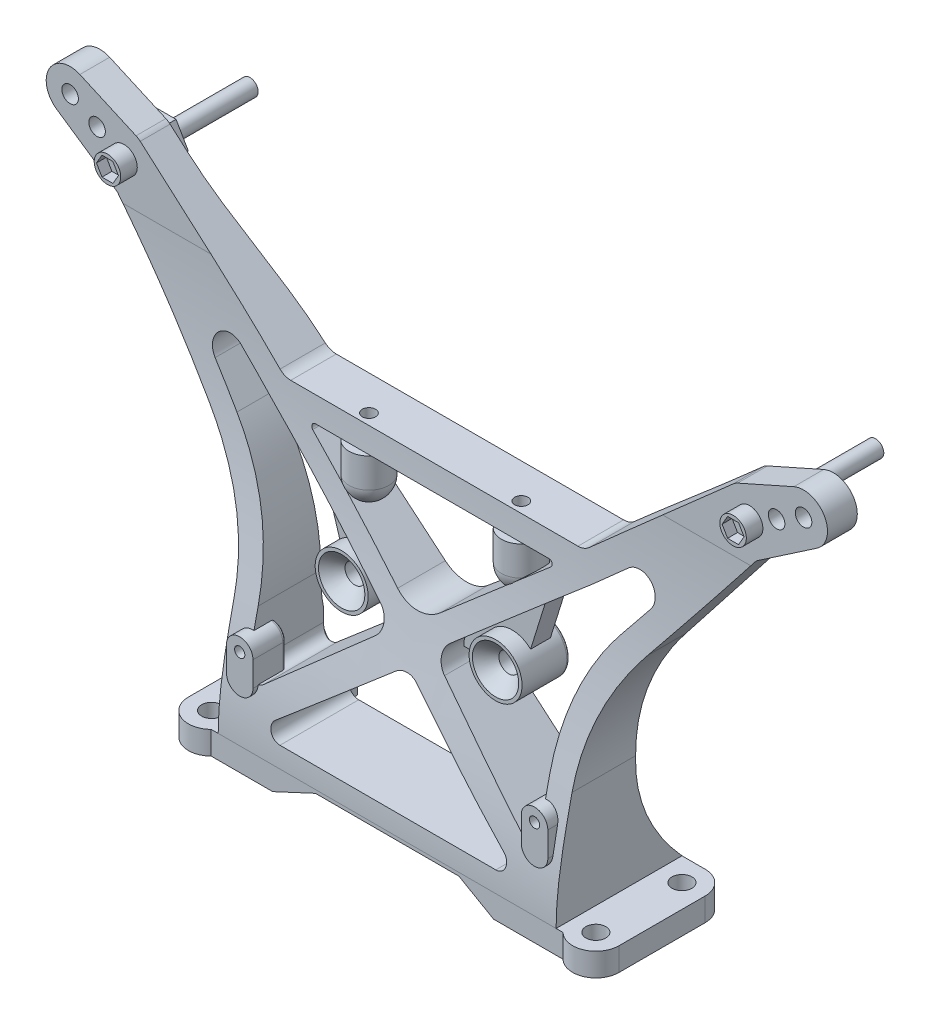
SolidWorks part; units mm, degrees
ref_plane "Front Plane" through (0, 0, 0) normal (0, 0, 1) x (1, 0, 0)
ref_plane "Top Plane" through (0, 0, 0) normal (0, 1, 0) x (1, 0, 0)
ref_plane "Right Plane" through (0, 0, 0) normal (1, 0, 0) x (0, 0, -1)
sketch "Sketch3" plane through (0, 0, 0) normal (0, 0, 1) x (1, 0, 0)
  line L0 (-16.289, -29.1062) -> (16.289, -29.1062)
  line L1 (17.2472, -26.4522) -> (1.597, -13.4575)
  line L2 (-1.597, -13.4575) -> (-17.2472, -26.4522)
  line L3 (32.5, -35.6062) -> (-32.5, -35.6062)
  line L4 (0, -35.6062) -> (0, 0) construction
  line L5 (-17.276, -35.6062) -> (-10.8295, -32.6062)
  line L6 (-10.8295, -32.6062) -> (10.8295, -32.6062)
  line L7 (10.8295, -32.6062) -> (16.0567, -35.6062)
  line L8 (0, -32.6062) -> (0, 0) construction
  line L9 (32.5, -35.6062) -> (32.5, -32.1062)
  line L10 (32.5, -32.1062) -> (25.5, -32.1062)
  line L11 (-32.5, -35.6062) -> (-32.5, -32.1062)
  line L12 (-32.5, -32.1062) -> (-25.5, -32.1062)
  line L13 (-25.5, -32.1062) -> (-25.5, -15.5226)
  line L14 (25.5, -32.1062) -> (-25.5, -32.1062) construction
  line L15 (0, -32.1062) -> (0, 0) construction
  line L16 (25.5, -32.1062) -> (25.5, -15.5226)
  line L17 (48.2113, 23.5519) -> (33.0635, 4.2389)
  line L18 (48.2113, 23.5519) -> (57.3809, 29.792)
  line L19 (53.8787, 36.0818) -> (45.3992, 32.3095)
  line L20 (47.2129, 28.2727) -> (55.3477, 32.7798) construction
  line L21 (44.7626, 31.9011) -> (23.3308, 13.018)
  line L22 (21.6781, 12.3938) -> (-21.6781, 12.3938)
  line L23 (-17.6357, 8.8938) -> (17.6357, 8.8938)
  line L24 (24.247, 8.8938) -> (29.2451, 13.2975)
  line L25 (32.8714, 9.8727) -> (29.0184, 4.9603)
  line L26 (22, -14.978) -> (22, -22.0285)
  line L27 (55.3477, 36.3938) -> (64.3873, 36.3938) construction
  line L28 (0, -29.1062) -> (0, 0) construction
  line L29 (24.247, 8.8938) -> (5.2406, -7.0999)
  line L30 (5.2234, -10.9109) -> (19.5239, -23.1674)
  line L31 (0, 8.8938) -> (0, 0) construction
  line L32 (0, 12.3938) -> (0, 0) construction
  line L33 (-55.3477, 36.3938) -> (-64.3873, 36.3938) construction
  line L34 (-47.2129, 28.2727) -> (-55.3477, 32.7798) construction
  line L35 (-5.2234, -10.9109) -> (-19.5239, -23.1674)
  line L36 (-24.247, 8.8938) -> (-5.2406, -7.0999)
  line L37 (-22, -14.978) -> (-22, -22.0285)
  line L38 (-32.8714, 9.8727) -> (-29.0184, 4.9603)
  line L39 (-24.247, 8.8938) -> (-29.2451, 13.2975)
  line L40 (-44.7626, 31.9011) -> (-23.3308, 13.018)
  line L41 (-53.8787, 36.0818) -> (-45.3992, 32.3095)
  line L42 (-48.2113, 23.5519) -> (-57.3809, 29.792)
  line L43 (-48.2113, 23.5519) -> (-33.0635, 4.2389)
  line L44 (-17.9576, 8.0112) -> (-3.2193, -4.3909)
  line L45 (3.2193, -4.3909) -> (17.9576, 8.0112)
  line L46 (0, 8.8938) -> (0, 0) construction
  arc A0 (57.3809, 29.792) -> (53.8787, 36.0818) centre (55.3477, 32.7798) ccw
  circle A1 centre (55.3477, 32.7798) radius 1.25
  circle A2 centre (51.2803, 30.5262) radius 1.25
  circle A3 centre (47.2129, 28.2727) radius 1.25
  arc A4 (29.2451, 13.2975) -> (32.8714, 9.8727) centre (30.9008, 11.4184) cw
  arc A5 (5.2406, -7.0999) -> (5.2234, -10.9109) centre (6.8503, -9.0127) ccw
  arc A6 (1.597, -13.4575) -> (-1.597, -13.4575) centre (0, -15.3809) ccw
  arc A7 (-17.2472, -26.4522) -> (-16.289, -29.1062) centre (-16.289, -27.6062) ccw
  arc A8 (22, -22.0285) -> (19.5239, -23.1674) centre (20.5, -22.0285) cw
  arc A9 (16.289, -29.1062) -> (17.2472, -26.4522) centre (16.289, -27.6062) ccw
  arc A10 (-5.2406, -7.0999) -> (-5.2234, -10.9109) centre (-6.8503, -9.0127) cw
  arc A11 (-22, -22.0285) -> (-19.5239, -23.1674) centre (-20.5, -22.0285) ccw
  arc A12 (-29.2451, 13.2975) -> (-32.8714, 9.8727) centre (-30.9008, 11.4184) ccw
  circle A13 centre (-47.2129, 28.2727) radius 1.25
  circle A14 centre (-51.2803, 30.5262) radius 1.25
  circle A15 centre (-55.3477, 32.7798) radius 1.25
  arc A16 (-57.3809, 29.792) -> (-53.8787, 36.0818) centre (-55.3477, 32.7798) cw
  arc A17 (-3.2193, -4.3909) -> (3.2193, -4.3909) centre (0, -0.5652) ccw
  arc A18 (17.6357, 8.8938) -> (17.9576, 8.0112) centre (17.6357, 8.3938) cw
  arc A19 (-17.9576, 8.0112) -> (-17.6357, 8.8938) centre (-17.6357, 8.3938) cw
  arc A20 (45.3992, 32.3095) -> (44.7626, 31.9011) centre (46.4154, 30.0253) ccw
  arc A21 (-44.7626, 31.9011) -> (-45.3992, 32.3095) centre (-46.4154, 30.0253) ccw
  arc A22 (23.3308, 13.018) -> (21.6781, 12.3938) centre (21.6781, 14.8938) cw
  arc A23 (-21.6781, 12.3938) -> (-23.3308, 13.018) centre (-21.6781, 14.8938) cw
  spline S0 degree 3 poles (25.5, -15.5226) (25.5, -7.9528) (28.6451, -1.3945) (33.0635, 4.2389) knots 0 0 0 0 1 1 1 1
  spline S1 degree 3 poles (22, -14.978) (22, -7.3515) (24.5868, -0.6899) (29.0184, 4.9603) knots 0 0 0 0 1 1 1 1
  spline S2 degree 3 poles (-22, -14.978) (-22, -7.3515) (-24.5868, -0.6899) (-29.0184, 4.9603) knots 0 0 0 0 1 1 1 1
  spline S3 degree 3 poles (-25.5, -15.5226) (-25.5, -7.9528) (-28.6451, -1.3945) (-33.0635, 4.2389) knots 0 0 0 0 1 1 1 1
  point P90 (0, -7.0999)
  point P97 (45.0497, 32.154)
  point P100 (-45.0497, 32.154)
  point P103 (22.6223, 12.3938)
  point P106 (-22.6223, 12.3938)
  dimension "D7" = 2.5
  dimension "D8" = 2.5
  dimension "D9" = 2.5
  dimension "D15" = 2.5
  dimension "D16" = 1.5
  dimension "D18" = 5
  dimension "D19" = 0.5
  dimension "D20" = 2.5
  dimension "D2" = 65
  dimension "D3" = 3
  dimension "D4" = 3.5
  dimension "D5" = 3.5
  dimension "D6" = 32.6062
  dimension "D10" = 72
  dimension "D11" = 48
  dimension "D12" = 3.5
  dimension "D13" = 25.5
  dimension "D14" = 3.5
  dimension "D17" = 45.2446
extrude "Boss-Extrude2" add sketch "Sketch3" along normal blind 8.5 and the other way blind 11.5 contours S3 L13 L12 L11 L3 L5 L6 L7 L9 L10 L16 S0 L17 L18 A0 L19 A20 L21 A22 L22 A23 L40 A21 L41 A16 L42 L43 S1 L26 A8 L30 A5 L29 L24 A4 L25 A14 A1 A2 A3 A9 L0 A7 L2 region at (24.2784, -34.2246, 0)
sketch "Sketch4" plane through (0, 0, 0) normal (1, 0, 0) x (0, 0, -1)
  line L0 (-8.5, -32.1062) -> (-7.5, -32.1062)
  line L1 (0, 36.3938) -> (0, 22.4957)
  line L2 (11.5, 36.3938) -> (-8.5, 36.3938) construction
  line L3 (0, 36.3938) -> (-8.5, 36.3938)
  line L4 (-8.5, 36.3938) -> (-8.5, 29.792) construction
  line L5 (-8.5, 36.3938) -> (-8.5, -32.1062)
  line L6 (4.5, 36.3938) -> (4.5, -16.1942)
  line L7 (4.5, 36.3938) -> (11.5, 36.3938)
  line L8 (11.5, 29.792) -> (11.5, 36.3938) construction
  line L9 (11.5, 36.3938) -> (11.5, -32.1062)
  line L10 (11.5, -32.1062) -> (-8.5, -32.1062) construction
  line L11 (-7.5, -32.1062) -> (-7.5, -34.5604) construction
  spline S0 degree 3 poles (-7.5, -32.1062) (-7.5, -18.2378) (0, -3.8629) (0, 22.4957) knots 0 0 0 0 1 1 1 1
  spline S1 degree 2 poles (4.5, -16.1942) (4.5, -24.3843) (11.5, -32.1062) knots 0 0 0 1 1 1
  dimension "D1" = 4.5
  dimension "D2" = 1
extrude "Cut-Extrude1" cut sketch "Sketch4" against normal through all and the other way through all contours L5 L1 L3 | L6 S1 region at (0, 10.6256, 4.9394) region at (0, 4.6469, -8.1165)
sketch "Sketch5" plane through (0, -35.6062, 0) normal (0, -1, 0) x (1, 0, 0)
  line L0 (-30.5, 5) -> (-30.5, 1.3765) construction
  line L1 (-29, 6.5) -> (-22.1667, 6.5) construction
  line L2 (-17.276, 8.5) -> (-32.5, 8.5) construction
  line L3 (-32.5, -11.5) -> (-32.5, 8.5) construction
  line L4 (-29, 3.5) -> (-29, -6.5) construction
  line L5 (-27.5, -8) -> (27.5, -8) construction
  line L6 (29, -6.5) -> (29, 3.5) construction
  line L7 (27.5, 5) -> (-27.5, 5) construction
  line L8 (-29, -9.5) -> (-25.3589, -9.5) construction
  line L9 (-17.276, -11.5) -> (-32.5, -11.5) construction
  line L10 (30.5, 5) -> (30.5, 0.9382) construction
  line L11 (32.5, -11.5) -> (32.5, 8.5) construction
  line L12 (32.5, -11.5) -> (16.0567, -11.5) construction
  line L13 (32.5, 8.5) -> (16.0567, 8.5) construction
  line L14 (26.5505, 7.5) -> (-26.5505, 7.5)
  line L15 (-29, -11.5) -> (-23.5, -11.5)
  line L16 (-23.5, -11.5) -> (-23.5, -7.5)
  line L17 (-20.5, -4.5) -> (-9.3284, -4.5)
  line L18 (-7.9142, -3.9142) -> (-6.0858, -2.0858)
  line L19 (-4.6716, -1.5) -> (4.6716, -1.5)
  line L20 (-33.0635, -4.5) -> (-48.2113, -4.5) construction
  line L21 (0, -1.5) -> (0, 0) construction
  line L22 (23.5, -11.5) -> (23.5, -7.5)
  line L23 (20.5, -4.5) -> (9.3284, -4.5)
  line L24 (7.9142, -3.9142) -> (6.0858, -2.0858)
  line L25 (-23.5, -11.5) -> (23.5, -11.5)
  line L26 (-29, -11.5) -> (-32.5, -11.5)
  line L27 (-32.5, -11.5) -> (-32.5, -8)
  line L28 (-32.5, 5) -> (-32.5, 8.5)
  line L29 (-32.5, 8.5) -> (-29, 8.5)
  line L30 (-29, 8.5) -> (29, 8.5)
  line L31 (29, 8.5) -> (32.5, 8.5)
  line L32 (32.5, 8.5) -> (32.5, 5)
  line L33 (32.5, -8) -> (32.5, -11.5)
  line L34 (32.5, -11.5) -> (29, -11.5)
  line L35 (9.3284, -4.5) -> (-9.3284, -4.5)
  circle A0 centre (-29, -8) radius 1.5
  circle A1 centre (-29, 5) radius 1.5
  circle A2 centre (29, 5) radius 1.5
  circle A3 centre (29, -8) radius 1.5
  arc A4 (-32.5, 5) -> (-29, 8.5) centre (-29, 5) cw
  arc A5 (-32.5, -8) -> (-29, -11.5) centre (-29, -8) ccw
  arc A6 (32.5, -8) -> (29, -11.5) centre (29, -8) cw
  arc A7 (32.5, 5) -> (29, 8.5) centre (29, 5) ccw
  arc A8 (-29, 8.5) -> (-26.5505, 7.5) centre (-29, 5) cw
  arc A9 (29, 8.5) -> (26.5505, 7.5) centre (29, 5) ccw
  arc A10 (-20.5, -4.5) -> (-23.5, -7.5) centre (-20.5, -7.5) ccw
  arc A11 (-4.6716, -1.5) -> (-6.0858, -2.0858) centre (-4.6716, -3.5) ccw
  arc A12 (-7.9142, -3.9142) -> (-9.3284, -4.5) centre (-9.3284, -2.5) cw
  arc A13 (20.5, -4.5) -> (23.5, -7.5) centre (20.5, -7.5) cw
  arc A14 (7.9142, -3.9142) -> (9.3284, -4.5) centre (9.3284, -2.5) ccw
  arc A15 (4.6716, -1.5) -> (6.0858, -2.0858) centre (4.6716, -3.5) cw
  point P55 (-23.5, -4.5)
  point P60 (-5.5, -1.5)
  point P63 (-8.5, -4.5)
  point P71 (8.5, -4.5)
  line M17 (32.5, -11.5) -> (32.5, 8.5)
  line M18 (32.5, 8.5) -> (16.0567, 8.5)
  line M19 (16.0567, 8.5) -> (16.0567, -11.5)
  line M20 (16.0567, -11.5) -> (32.5, -11.5)
  dimension "D3" = 3
  dimension "D4" = 3
  dimension "D5" = 3
  dimension "D6" = 3
  dimension "D14" = 3
  dimension "D15" = 2
  dimension "D1" = 2
  dimension "D2" = 2
  dimension "D7" = 2
  dimension "D8" = 2
  dimension "D9" = 1
  dimension "D10" = 9
  dimension "D11" = 15
  dimension "D12" = 3
  dimension "D13" = 5.5
extrude "Cut-Extrude2" cut sketch "Sketch5" against normal through all contours A13 L23 L22 M19 M20 | L17 A10 L16 L25 L23 L35 M19 | A3 | A6 M17 M20 | A7 M17 M18 | A2 | A9 L14 M18 M19 | L30 A8 L14 M19 | L28 A4 L29 | A1 | A0 | A5 L27 L26 region at (21.6996, -35.6062, 8.0142) region at (-31.7182, -35.6062, 7.7182) region at (-31.7182, -35.6062, -10.7182) region at (-5.6323, -35.6062, 8.0037) region at (31.7182, -35.6062, 7.7182) region at (-3.5874, -35.6062, -8.0199) region at (19.6609, -35.6062, -8.1089) region at (31.7182, -35.6062, -10.7182) region at (-29, -35.6062, -8) region at (-29, -35.6062, 5) region at (29, -35.6062, 5) region at (29, -35.6062, -8)
ref_plane "Plane2" through (0, 0, -2.25) normal (0, 0, -1) x (-1, 0, 0)
sketch "Sketch7" plane through (0, 0, -4.5) normal (0, 0, -1) x (-1, 0, 0)
  line L8 (-21.6781, 12.3938) -> (21.6781, 12.3938)
  line L9 (-44.7626, 31.9011) -> (-23.3308, 13.018)
  line L10 (-21.6781, 12.3938) -> (21.6781, 12.3938)
  line L11 (-44.7626, 31.9011) -> (-23.3308, 13.018)
  line L12 (23.3308, 13.018) -> (44.7626, 31.9011)
  line L13 (23.3308, 13.018) -> (44.7626, 31.9011)
  line L14 (17.6357, 8.8938) -> (22.3586, 8.8938)
  line L15 (-17.6357, 8.8938) -> (17.6357, 8.8938)
  line L16 (-17.6357, 8.8938) -> (17.6357, 8.8938)
  line L17 (-17.6357, 8.8938) -> (-22.3586, 8.8938)
  line L20 (-29.2451, 13.2975) -> (-24.247, 8.8938)
  line L21 (-29.2451, 13.2975) -> (-25.664, 10.1422)
  line L22 (29.2451, 13.2975) -> (44.5347, 26.7688)
  line L23 (29.2451, 13.2975) -> (24.247, 8.8938)
  line L24 (29.2451, 13.2975) -> (25.664, 10.1422)
  line L25 (44.5347, 26.7688) -> (42.0886, 29.5451)
  line L26 (-29.2451, 13.2975) -> (-44.5347, 26.7688)
  line L27 (-44.5347, 26.7688) -> (-42.0886, 29.5451)
  arc A4 (22.3586, 8.8938) -> (25.664, 10.1422) centre (22.3586, 13.8938) ccw
  arc A5 (-25.664, 10.1422) -> (-22.3586, 8.8938) centre (-22.3586, 13.8938) ccw
  arc A6 (21.6781, 12.3938) -> (23.3308, 13.018) centre (21.6781, 14.8938) ccw
  arc A7 (-23.3308, 13.018) -> (-21.6781, 12.3938) centre (-21.6781, 14.8938) ccw
  arc A8 (21.6781, 12.3938) -> (23.3308, 13.018) centre (21.6781, 14.8938) ccw
  arc A9 (-23.3308, 13.018) -> (-21.6781, 12.3938) centre (-21.6781, 14.8938) ccw
  dimension "D8" = 5
  dimension "D6" = 25
  dimension "D7" = 25
  dimension "D1" = 0
  dimension "D2" = 0
  dimension "D3" = 0
  dimension "D4" = 0
  dimension "D5" = 0
extrude "Boss-Extrude3" add sketch "Sketch7" along normal blind 2 contours A9 L11 L27 L26 L21 A5 L17 L16 L14 A4 L24 L22 L25 L13 A8 L10 region at (0, 11.4794, -4.5)
sketch "Sketch8" plane through (3.7391, -4.2438, 0) normal (-0.6611, 0.7503, 0) x (0.7503, 0.6611, 0)
  line L0 (26.1113, 6.5) -> (22.2063, 6.5) construction
  line L1 (24.4586, 6.5) -> (-8.072, 6.5) construction
  line L2 (51.1113, 4.5) -> (53.234, 4.5) construction
  line L3 (51.1113, 4.5) -> (54.6753, 4.5) construction
  line L4 (26.1113, 6.5) -> (51.1113, 6.5)
  line L5 (51.1113, 6.5) -> (51.1113, 4.5)
  spline S0 degree 3 poles (26.1113, 6.5) (34.5244, 6.5) (42.7514, 4.5) (51.1113, 4.5) knots 0 0 0 0 1 1 1 1
extrude "Cut-Extrude3" cut sketch "Sketch8" against normal up to surface (3.7002 mm away) up to face at (30.6103, 14.5003, -3.7264)
mirror "Mirror1" about plane through (0, 0, 0) normal (1, 0, 0) of "Cut-Extrude3"
ref_plane "Plane3" through (0, 0, -1.25) normal (0, 0, 1) x (1, 0, 0)
sketch "Sketch10" plane through (0, 0, -1.25) normal (0, 0, 1) x (1, 0, 0)
  line L0 (-11.5, 8.8938) -> (-11.5, 1.4265)
  line L2 (-8.5, 4.4265) -> (-8.5, 8.8938)
  line L3 (-8.5, 8.8938) -> (-11.5, 8.8938)
  arc A0 (-11.5, 1.4265) -> (-8.5, 4.4265) centre (-11.5, 4.4265) ccw
  dimension "D2" = 3
  dimension "D1" = 11.5
revolve "Revolve1" add sketch "Sketch10" angle 360 about L0 region at (-10.0783, 5.4492, -1.25)
mirror "Mirror3" about plane through (0, 0, 0) normal (1, 0, 0) of "Revolve1"
sketch "Sketch11" plane through (0, 12.3938, 0) normal (0, 1, 0) x (1, 0, 0)
  line L0 (11.5, 1.25) -> (-11.5, 1.25) construction
  line L1 (0, 0) -> (0, 1.25) construction
  circle A0 centre (-11.5, 1.25) radius 1
  circle A1 centre (11.5, 1.25) radius 1
  dimension "D2" = 2
  dimension "D3" = 2
  dimension "D1" = 1.25
  dimension "D4" = 23
extrude "Cut-Extrude4" cut sketch "Sketch11" against normal blind 8
sketch "Sketch13" plane through (0, 0, -1.25) normal (0, 0, 1) x (1, 0, 0)
  line L0 (-16.661, 2.5102) -> (-12.967, -9.4)
  line L1 (-24.247, 8.8938) -> (-5.2406, -7.0999) construction
  line L2 (-12.967, -9.4) -> (12.967, -9.4)
  line L3 (12.967, -9.4) -> (16.661, 2.5102)
  line L4 (5.2406, -7.0999) -> (24.247, 8.8938) construction
  line L5 (-16.661, 2.5102) -> (16.661, 2.5102) construction
  line L8 (-5.2406, -7.0999) -> (-24.247, 8.8938)
  line L9 (-5.2406, -7.0999) -> (-24.247, 8.8938)
  line L11 (0, -9.4) -> (0, 0) construction
  line L12 (24.247, 8.8938) -> (5.2406, -7.0999)
  line L13 (24.247, 8.8938) -> (5.2406, -7.0999)
  arc A2 (-5.2234, -10.9109) -> (-5.2406, -7.0999) centre (-6.8503, -9.0127) ccw
  arc A3 (-5.2234, -10.9109) -> (-5.2406, -7.0999) centre (-6.8503, -9.0127) ccw
  arc A4 (5.2406, -7.0999) -> (5.2234, -10.9109) centre (6.8503, -9.0127) ccw
  arc A5 (5.2406, -7.0999) -> (5.2234, -10.9109) centre (6.8503, -9.0127) ccw
  dimension "D2" = 9.4
  dimension "D1" = 0
  dimension "D3" = 0
extrude "Boss-Extrude5" add sketch "Sketch13" along normal blind 1.5 and the other way blind 1.5 contours L13 A5 L2 L3 | L2 A3 L9 L0 region at (-10.8954, -5.3406, -1.25) region at (10.8954, -5.3406, -1.25)
sketch "Sketch14" plane through (0, 0, 0.25) normal (0, 0, 1) x (1, 0, 0)
  line L0 (11.614, -7.6515) -> (-11.614, -7.6515) construction
  line L1 (0, -7.6515) -> (0, 0) construction
  circle A0 centre (-11.614, -7.6515) radius 4
  circle A1 centre (11.614, -7.6515) radius 4
  dimension "D1" = 8
  dimension "D2" = 8
extrude "Boss-Extrude6" add sketch "Sketch14" along normal blind 2.5 and the other way up to surface (4.75 mm away) other way up to face at (0, -23.0213, -4.5)
sketch "Sketch15" plane through (0, 0, 2.75) normal (0, 0, 1) x (1, 0, 0)
  circle A0 centre (-11.614, -7.6515) radius 1.5
  circle A1 centre (11.614, -7.6515) radius 1.5
  circle A2 centre (11.614, -7.6515) radius 4 construction
  circle A3 centre (-11.614, -7.6515) radius 4 construction
  dimension "D1" = 3
  dimension "D2" = 3
extrude "Cut-Extrude5" cut sketch "Sketch15" against normal through all
chamfer "Chamfer1" distance 2 angle 45 2 edges at (13.114, -7.6515, 2.75) (-10.114, -7.6515, 2.75)
fillet "Fillet1" radius 0.5 2 edges at (-11.614, -11.6515, -4.5) (11.614, -11.6515, -4.5)
sketch "Sketch16" plane through (0, 0, 7.5) normal (0, 0, 1) x (1, 0, 0)
  line L0 (-22.25, -19.8562) -> (-22.25, -23.6062) construction
  line L1 (-20.25, -19.8562) -> (-20.25, -23.6062)
  line L2 (-24.25, -19.8562) -> (-24.25, -23.6062)
  line L3 (-17.276, -35.6062) -> (-26.5505, -35.6062) construction
  line L4 (-25.5, -15.5226) -> (-25.5, -32.1062) construction
  arc A0 (-20.25, -19.8562) -> (-24.25, -19.8562) centre (-22.25, -19.8562) ccw
  arc A1 (-24.25, -23.6062) -> (-20.25, -23.6062) centre (-22.25, -23.6062) ccw
  point P2 (-22.25, -21.7312)
  point P9 (-24.25, -21.7312)
  dimension "D1" = 12
  dimension "D2" = 4
  dimension "D3" = 1.25
  dimension "D4" = 15.75
extrude "Boss-Extrude7" add sketch "Sketch16" against normal blind 5 contours A0 L2 A1 L1
fillet "Fillet2" radius 0.5 2 edges at (-20.25, -21.6819, 2.5) (-20.75, -18.5334, 2.5)
sketch "Sketch17" plane through (0, 0, 7.5) normal (0, 0, 1) x (1, 0, 0)
  circle A0 centre (-22.25, -19.8562) radius 0.7707
  arc A1 (-20.25, -19.8562) -> (-24.25, -19.8562) centre (-22.25, -19.8562) ccw construction
extrude "Cut-Extrude6" cut sketch "Sketch17" against normal blind 4 contours A0
mirror "Mirror5" about plane through (0, 0, 0) normal (1, 0, 0) of "Cut-Extrude6", "Fillet2", "Boss-Extrude7"
ref_axis "Axis1" through (-11.5, 4.3938, -1.25) along (0, 1, 0)
ref_axis "Axis2" through (11.5, 4.3938, -1.25) along (0, 1, 0)
ref_plane "Plane4" through (0, 0, -1.25) normal (0, 0, -1) x (-1, 0, 0)
sketch "Sketch18" plane through (0, 0, 0) normal (0, 0, 1) x (1, 0, 0)
  circle A0 centre (-47.2129, 28.2727) radius 2
  dimension "D1" = 4
extrude "Boss-Extrude8" add sketch "Sketch18" along normal blind 2.5
sketch "Sketch19" plane through (0, 0, 2.5) normal (0, 0, 1) x (1, 0, 0)
  circle A0 centre (-47.2129, 28.2727) radius 1.25
  dimension "D1" = 2.5
extrude "Boss-Extrude9" add sketch "Sketch19" against normal blind 21.5
sketch "Sketch20" plane through (0, 0, 2.5) normal (0, 0, 1) x (1, 0, 0)
  line L1 (-46.3851, 29.7065) -> (-48.0408, 29.7065)
  line L2 (-48.0408, 29.7065) -> (-48.8686, 28.2727)
  line L3 (-48.8686, 28.2727) -> (-48.0408, 26.8388)
  line L4 (-48.0408, 26.8388) -> (-46.3851, 26.8388)
  line L5 (-46.3851, 26.8388) -> (-45.5572, 28.2727)
  line L6 (-45.5572, 28.2727) -> (-46.3851, 29.7065)
  circle A0 centre (-47.2129, 28.2727) radius 1.4339 construction
extrude "Cut-Extrude7" cut sketch "Sketch20" against normal blind 1.5
sketch "Sketch21" plane through (0, 0, -4.5) normal (0, 0, -1) x (-1, 0, 0)
  line L1 (45.3623, 31.478) -> (43.5118, 28.2727)
  line L2 (43.5118, 28.2727) -> (45.3623, 25.0674)
  line L3 (45.3623, 25.0674) -> (49.0635, 25.0674)
  line L4 (49.0635, 25.0674) -> (50.9141, 28.2727)
  line L5 (50.9141, 28.2727) -> (49.0635, 31.478)
  line L6 (49.0635, 31.478) -> (45.3623, 31.478)
  circle A0 centre (47.2129, 28.2727) radius 1.25
  circle A1 centre (47.2129, 28.2727) radius 1.25 construction
  circle A2 centre (47.2129, 28.2727) radius 3.2053 construction
extrude "Boss-Extrude10" add sketch "Sketch21" along normal blind 1.5
mirror "Mirror6" about plane through (0, 0, 0) normal (1, 0, 0) of "Boss-Extrude10", "Cut-Extrude7", "Boss-Extrude9", "Boss-Extrude8"
